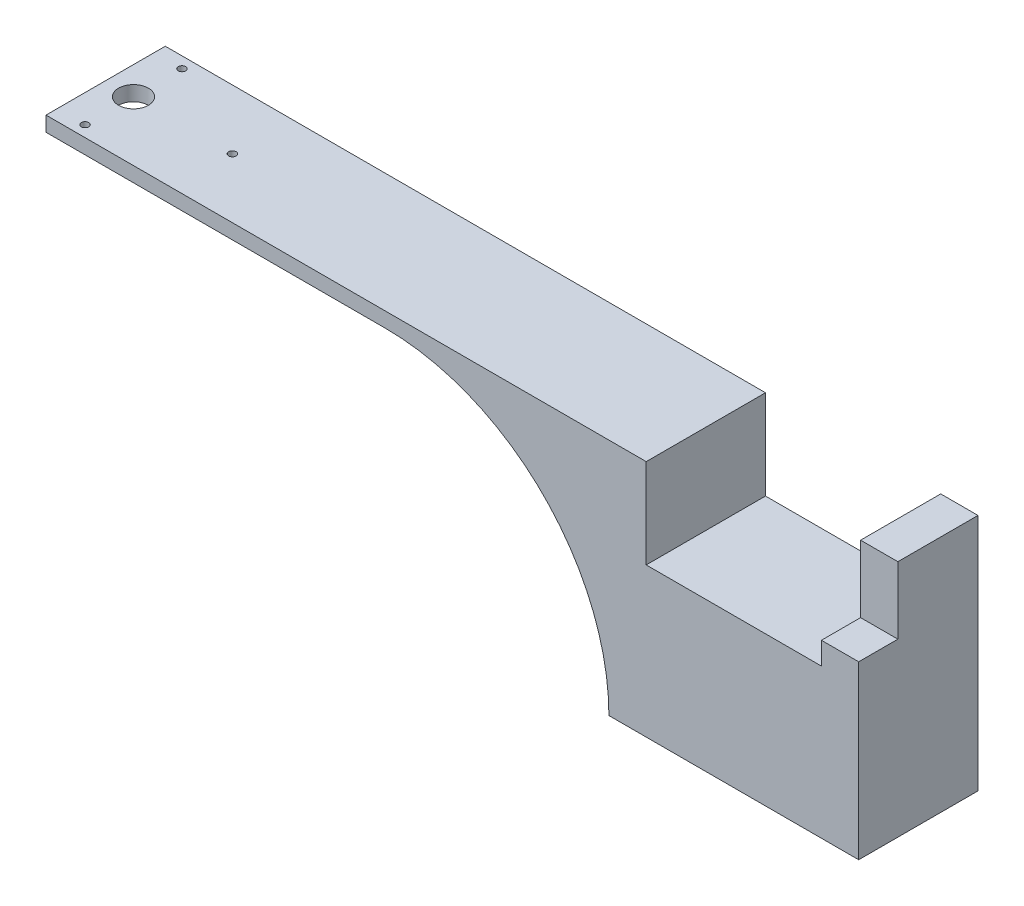
SolidWorks part; units mm, degrees
material "ABS"
ref_plane "Front Plane" through (0, 0, 0) normal (0, 0, 1) x (1, 0, 0)
ref_plane "Top Plane" through (0, 0, 0) normal (0, 1, 0) x (1, 0, 0)
ref_plane "Right Plane" through (0, 0, 0) normal (1, 0, 0) x (0, 0, -1)
sketch "Sketch1" plane through (0, 0, 0) normal (0, 1, 0) x (1, 0, 0)
  line L0 (-55, 0) -> (55, 0) construction
  line L1 (16.75, -8) -> (-16.75, -8)
  line L2 (16.75, -8) -> (16.75, 8)
  line L3 (16.75, 8) -> (-16.75, 8)
  line L4 (-16.75, -8) -> (-16.75, 8)
  line L5 (0, -55) -> (0, 55) construction
  dimension "D1" = 33.5
  dimension "D2" = 16
  dimension "D3" = 8
  dimension "D4" = 16.75
extrude "Boss-Extrude1" add sketch "Sketch1" along normal blind 32
sketch "Sketch2" plane through (0, 32, 0) normal (0, 1, 0) x (1, 0, 0)
  line L0 (-16.75, -8) -> (16.75, -8) construction
  line L1 (-11.75, -8) -> (11.75, -8)
  line L2 (-11.75, -8) -> (-11.75, 8)
  line L3 (-11.75, 8) -> (11.75, 8)
  line L4 (11.75, -8) -> (11.75, 8)
  line L5 (16.75, 8) -> (-16.75, 8) construction
  line L6 (-16.75, 8) -> (-16.75, -8) construction
  dimension "D1" = 23.5
  dimension "D2" = 5
extrude "Cut-Extrude1" cut sketch "Sketch2" against normal blind 12
sketch "Sketch4" plane through (0, 0, 0) normal (0, -1, 0) x (-1, 0, 0)
  line L0 (-55, 0) -> (55, 0) construction
  circle A0 centre (15.8132, -7.1225) radius 0.5
  circle A1 centre (-15.8688, -7.1225) radius 0.5
  circle A2 centre (-15.8688, 7.1225) radius 0.5
  circle A3 centre (15.8132, 7.1225) radius 0.5
extrude "Boss-Extrude2" add sketch "Sketch4" along normal blind 0.5
fillet "Fillet1" radius 0.5 4 edges at (-15.8132, -0.5, -6.6225) (15.8688, -0.5, -6.6225) (15.8688, -0.5, 6.6225) (-15.8132, -0.5, 6.6225)
sketch "Sketch6" plane through (-16.75, 0, 0) normal (-1, 0, 0) x (0, 0, 1)
  line L0 (8, 32) -> (8, 0) construction
  line L1 (-8, 32) -> (8, 32)
  line L2 (-8, 32) -> (-8, 30)
  line L3 (-8, 30) -> (8, 30)
  line L4 (8, 32) -> (8, 30)
  dimension "D1" = 2
extrude "Boss-Extrude3" add sketch "Sketch6" along normal blind 75.5
sketch "Sketch7" plane through (0, 32, 0) normal (0, 1, 0) x (1, 0, 0)
  line L0 (16.75, -8) -> (16.75, 8) construction
  line L1 (11.75, -8) -> (16.75, -8)
  line L2 (11.75, -8) -> (11.75, -2.7474)
  line L3 (11.75, -2.7474) -> (16.75, -2.7474)
  line L4 (16.75, -8) -> (16.75, -2.7474)
extrude "Cut-Extrude2" cut sketch "Sketch7" against normal blind 9
sketch "Sketch8" plane through (0, 0, 0) normal (0, 0, 1) x (1, 0, 0)
  line L0 (-11.75, 20) -> (-11.75, 32) construction
  line L1 (11.75, 20) -> (-11.75, 20) construction
  circle A0 centre (13.65, 26) radius 0.8
  circle A1 centre (-13.65, 26) radius 0.8
  dimension "D2" = 27.3
  dimension "D1" = 6
  dimension "D3" = 1.9
extrude "Cut-Extrude3" cut sketch "Sketch8" against normal blind 8
sketch "Sketch9" plane through (0, 32, 0) normal (0, 1, 0) x (1, 0, 0)
  line L0 (-17.875, 0) -> (17.875, 0) construction
  line L1 (-92.25, -8) -> (-92.25, 8) construction
  circle A0 centre (-88.516, 6.5) radius 0.5
  circle A1 centre (-75.25, 0) radius 0.5
  circle A2 centre (-88.516, -6.5) radius 0.5
  circle A3 centre (-88.516, 0) radius 2
  dimension "D1" = 6.5
  dimension "D2" = 17
extrude "Cut-Extrude4" cut sketch "Sketch9" against normal blind 8
fillet "Fillet2" radius 30 1 edges at (-16.75, 30, 0)
